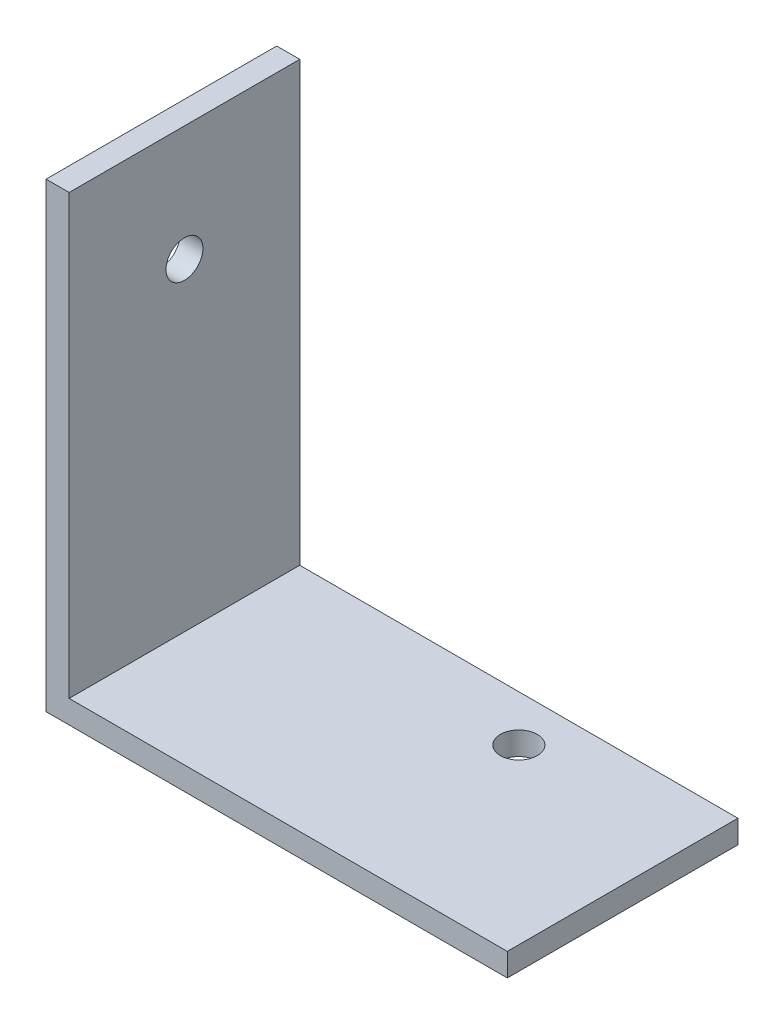
SolidWorks part; units mm, degrees
material "1060 Сплав"
ref_plane "Спереди" through (0, 0, 0) normal (0, 0, 1) x (1, 0, 0)
ref_plane "Сверху" through (0, 0, 0) normal (0, 1, 0) x (1, 0, 0)
ref_plane "Справа" through (0, 0, 0) normal (1, 0, 0) x (0, 0, -1)
sketch "Эскиз1" plane through (0, 0, 0) normal (0, 0, 1) x (1, 0, 0)
  line L0 (0, 0) -> (40, 0)
  line L1 (40, 0) -> (40, 2)
  line L2 (40, 2) -> (2, 2)
  line L3 (2, 2) -> (2, 40)
  line L4 (2, 40) -> (0, 40)
  line L5 (0, 40) -> (0, 0)
  dimension "D1" = 40
  dimension "D2" = 2
  dimension "D3" = 40
extrude "Бобышка-Вытянуть1" add sketch "Эскиз1" along normal blind 20
sketch "Эскиз2" plane through (0, 0, 0) normal (0, -1, 0) x (1, 0, 0)
  arc A0 (26.6, 4) -> (23.4, 4) centre (25, 4) ccw construction
  arc A1 (26.6, 4) -> (23.4, 4) centre (25, 4) ccw construction
  circle A2 centre (25, 4) radius 1.6
extrude "Вырез-Вытянуть1" cut sketch "Эскиз2" against normal through all
sketch "Эскиз3" plane through (0, 0, 0) normal (-1, 0, 0) x (0, 0, 1)
  line L0 (10, 40) -> (10, 0) construction
  line L1 (20, 40) -> (0, 40) construction
  line L2 (20, 0) -> (0, 0) construction
  circle A0 centre (10, 30) radius 1.6
  dimension "D1" = 3.2
  dimension "D2" = 10
extrude "Вырез-Вытянуть2" cut sketch "Эскиз3" against normal through all
